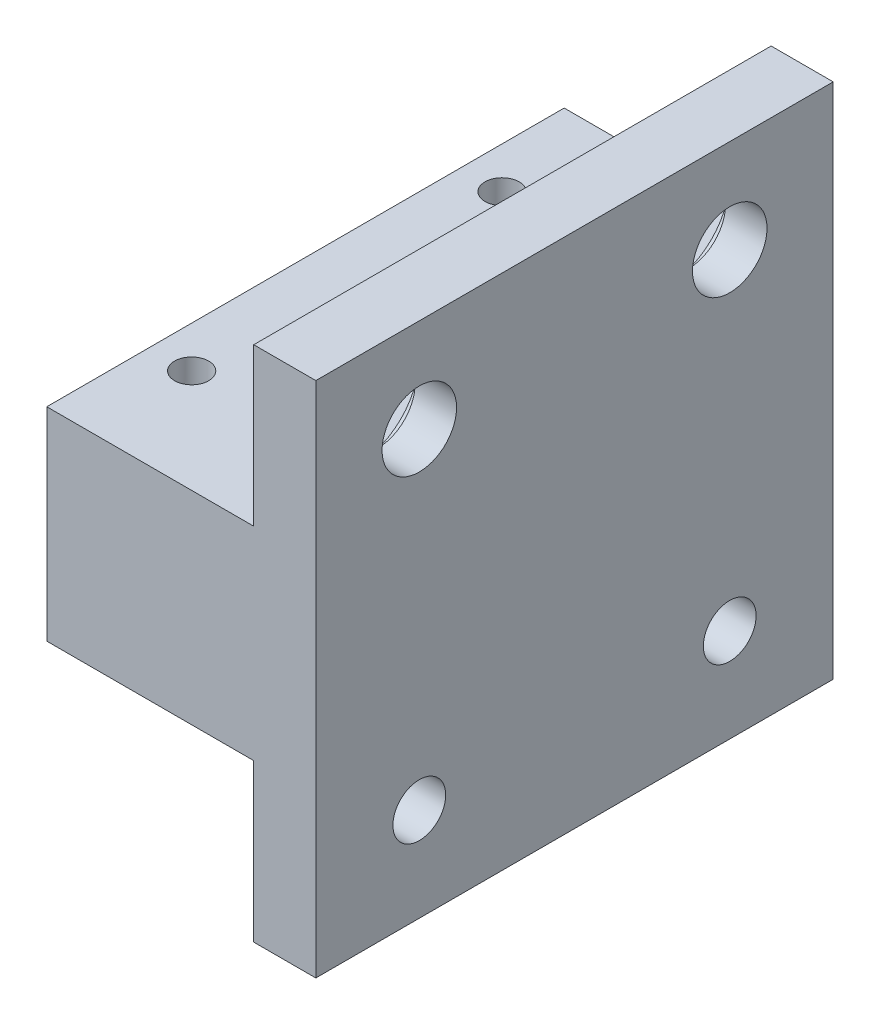
SolidWorks part; units mm, degrees
ref_plane "Front" through (0, 0, 0) normal (0, 0, 1) x (1, 0, 0)
ref_plane "Top" through (0, 0, 0) normal (0, 1, 0) x (1, 0, 0)
ref_plane "Right" through (0, 0, 0) normal (1, 0, 0) x (0, 0, -1)
sketch "Sketch2" plane through (0, 0, 0) normal (1, 0, 0) x (0, 0, -1)
  line L1 (-25, -25) -> (25, -25)
  line L2 (-25, -25) -> (-25, 25)
  line L3 (-25, 25) -> (25, 25)
  line L4 (25, -25) -> (25, 25)
  line L5 (0, 25) -> (0, -25) construction
  line L6 (-25, 0) -> (25, 0) construction
  point P0 (0, 0)
  dimension "D1" = 50
  dimension "D2" = 50
extrude "Boss-Extrude1" add sketch "Sketch2" along normal blind 6
sketch "Sketch3" plane through (0, 0, 0) normal (-1, 0, 0) x (0, 0, 1)
  line L0 (-25, -25) -> (-25, 25) construction
  line L3 (-25, -9.8094) -> (25, -9.8094)
  line L4 (-25, -9.8094) -> (-25, 9.8094)
  line L6 (-25, 9.8094) -> (25, 9.8094)
  line L7 (25, -9.8094) -> (25, 9.8094)
  line L8 (25, 25) -> (25, -25) construction
  line L9 (-15, -2.6906) -> (15, -2.6906) construction
  line L10 (-19, -0.3812) -> (-19, 2.3094)
  line L11 (-15, -7.3094) -> (-11, -5)
  line L12 (-11, -5) -> (-11, -0.3812)
  line L13 (-11, -0.3812) -> (-15, 1.9282) construction
  line L14 (-15, 1.9282) -> (-19, -0.3812) construction
  line L15 (-19, -0.3812) -> (-19, -5)
  line L16 (-19, -5) -> (-15, -7.3094)
  line L17 (15, -7.3094) -> (19, -5)
  line L18 (19, -5) -> (19, -0.3812)
  line L19 (19, -0.3812) -> (15, 1.9282) construction
  line L20 (15, 1.9282) -> (11, -0.3812) construction
  line L21 (11, -0.3812) -> (11, -5)
  line L22 (11, -5) -> (15, -7.3094)
  line L23 (-11, 2.3094) -> (-11, -0.3812)
  line L24 (11, -0.3812) -> (11, 2.3094)
  line L25 (19, 2.3094) -> (19, -0.3812)
  line L26 (-25, 0) -> (25, 0) construction
  line L27 (0, 0) -> (0, -2.6906) construction
  circle A0 centre (-15, -2.6906) radius 4 construction
  circle A1 centre (15, -2.6906) radius 4 construction
  arc A2 (-19, 2.3094) -> (-11, 2.3094) centre (-15, 2.3094) cw
  arc A3 (11, 2.3094) -> (19, 2.3094) centre (15, 2.3094) cw
  dimension "D1" = 30
  dimension "D2" = 8
  dimension "D3" = 3.5
  dimension "D4" = 2.5
  dimension "D5" = 5
extrude "Boss-Extrude2" add sketch "Sketch3" along normal blind 20
sketch "Sketch5" plane through (0, 0, 0) normal (-1, 0, 0) x (0, 0, 1)
  line L0 (-19, -2.3094) -> (-11, -2.3094)
  line L1 (11, -2.3094) -> (19, -2.3094)
  line L4 (-19, 2.3094) -> (-19, -5)
  line L5 (-19, -5) -> (-15, -7.3094)
  line L6 (-15, -7.3094) -> (-11, -5)
  line L7 (-11, -5) -> (-11, 2.3094)
  line L8 (-19, -2.3094) -> (-19, -5)
  line L9 (-19, -5) -> (-15, -7.3094)
  line L10 (-15, -7.3094) -> (-11, -5)
  line L11 (-11, -5) -> (-11, -2.3094)
  line L12 (11, 2.3094) -> (11, -5)
  line L13 (11, -5) -> (15, -7.3094)
  line L14 (15, -7.3094) -> (19, -5)
  line L15 (19, -5) -> (19, 2.3094)
  line L16 (11, -2.3094) -> (11, -5)
  line L17 (11, -5) -> (15, -7.3094)
  line L18 (15, -7.3094) -> (19, -5)
  line L19 (19, -5) -> (19, -2.3094)
  circle A0 centre (-15, -2.6906) radius 4 construction
  arc A1 (-11, 2.3094) -> (-19, 2.3094) centre (-15, 2.3094) ccw
  arc A3 (19, 2.3094) -> (11, 2.3094) centre (15, 2.3094) ccw
  circle A5 centre (-15, 1.6906) radius 4 construction
  dimension "D3" = 8
  dimension "D4" = 5
  dimension "D1" = 0
  dimension "D2" = 0
extrude "Boss-Extrude3" add sketch "Sketch5" along normal blind 12
sketch "Sketch6" plane through (0, 0, 0) normal (1, 0, 0) x (0, 0, -1)
  line L1 (15, -15.95) -> (-15, -15.95) construction
  line L2 (15, -15.95) -> (15, 15.95) construction
  line L3 (15, 15.95) -> (-15, 15.95) construction
  line L4 (-15, -15.95) -> (-15, 15.95) construction
  line L5 (0, 15.95) -> (0, -15.95) construction
  line L6 (15, 0) -> (-15, 0) construction
  circle A0 centre (-15, 15.95) radius 3.6
  circle A1 centre (15, 15.95) radius 3.6
  circle A2 centre (-15, -15.95) radius 2.55
  circle A3 centre (15, -15.95) radius 2.55
  point P0 (0, 0)
  dimension "D3" = 7.2
  dimension "D4" = 5.1
  dimension "D1" = 31.9
  dimension "D2" = 30
extrude "Cut-Extrude2" cut sketch "Sketch6" along normal through all
sketch "Sketch7" plane through (0, 0, 0) normal (-1, 0, 0) x (0, 0, 1)
  circle A0 centre (-15, -15.95) radius 5.05
  circle A1 centre (15, -15.95) radius 5.05
  circle A2 centre (-15, 15.95) radius 6
  circle A3 centre (15, 15.95) radius 6
  dimension "D1" = 12
  dimension "D2" = 10.1
extrude "Cut-Extrude3" cut sketch "Sketch7" against normal blind 2
hole_wizard "M4x0.7 Tapped Hole1" positions "Sketch9" profile "Sketch10" tap size "M4x0.7" standard "ANSI Metric" end condition up to next
sketch "Sketch9" plane through (0, 9.8094, 0) normal (0, 1, 0) x (1, 0, 0)
  line L0 (-16, -15) -> (-16, 15) construction
  line L3 (-16, 0) -> (0, 0) construction
  line L5 (-20, -25) -> (-20, 25) construction
  point P0 (-16, 15)
  point P2 (-16, -15)
  dimension "D1" = 30
  dimension "D2" = 4
sketch "Sketch10" plane through (-16, 9.8094, -15) normal (1, 0, 0) x (0, 0, 1)
  line L0 (0, 0) -> (0, 3.5)
  line L1 (0, 3.5) -> (1.65, 3.5)
  line L2 (1.65, 3.5) -> (1.65, 0)
  line L5 (1.65, 0) -> (0, 0)
  line L11 (0, -6.35) -> (0, 107.95) construction
  dimension "Thread Major Dia." = 3.3
  dimension "Thru Tap Drill Depth" = 3.5
